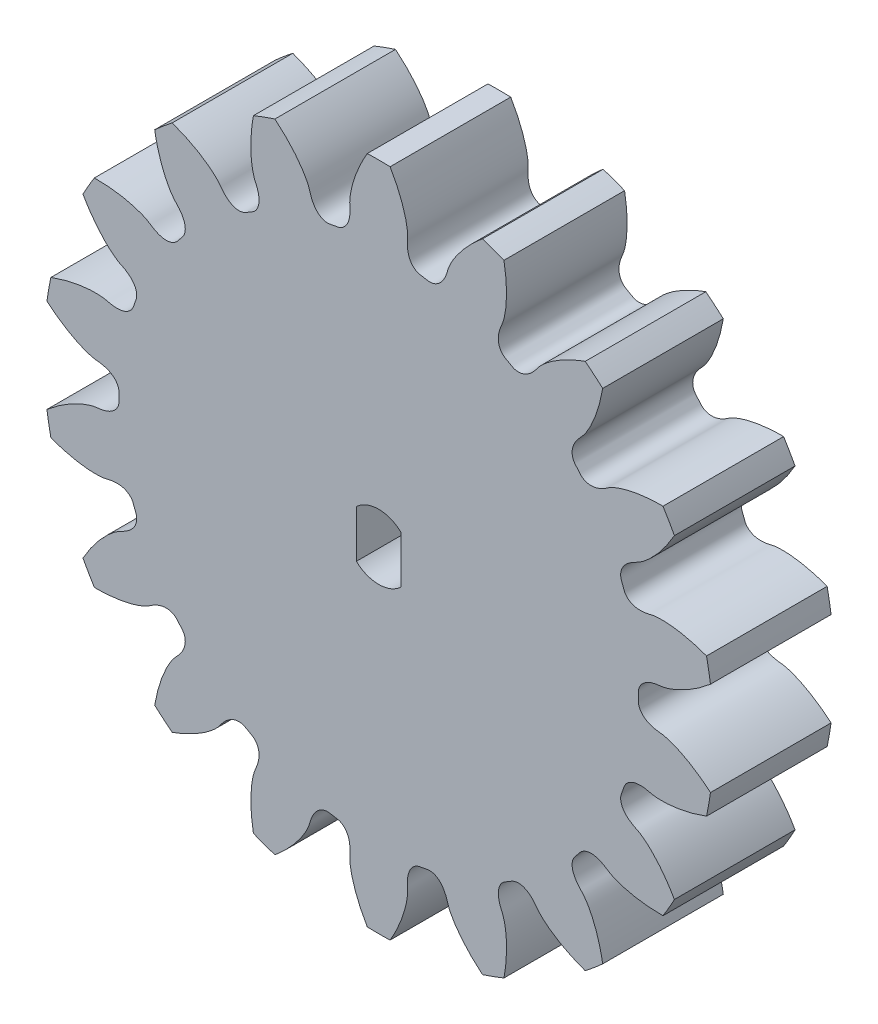
SolidWorks part; units mm, degrees
ref_plane "Front Plane" through (0, 0, 0) normal (0, 0, 1) x (1, 0, 0)
ref_plane "Top Plane" through (0, 0, 0) normal (0, 1, 0) x (1, 0, 0)
ref_plane "Right Plane" through (0, 0, 0) normal (1, 0, 0) x (0, 0, -1)
ref_axis "Axis1" through (0, 0, 55) along (0, 0, -1)
sketch "旋转草图小直齿轮" plane through (0, 0, 0) normal (1, 0, 0) x (0, 0, -1)
  line L0 (0, 0) -> (1, 0) construction
  line L1 (-5, 0) -> (-5, 27.7778)
  line L2 (-5, 27.7778) -> (5, 27.7778)
  line L3 (5, 27.7778) -> (5, 0)
  line L4 (5, 0) -> (-5, 0)
  dimension "Side1" = 5
  dimension "OutsideRadius" = 27.7778
  dimension "Side2" = 5
revolve "小直齿轮" add sketch "旋转草图小直齿轮" angle 360 about L0
sketch "齿草图小直齿轮" plane through (0, 0, 0) normal (0, 0, 1) x (1, 0, 0)
  arc A0 (27.6292, 3.9957) -> (27.6292, -3.9957) centre (0, 0) cw
  spline S0 degree 3 poles (27.6292, -3.9957) (27.2908, -3.7024) (26.835, -3.3411) (26.2533, -2.941) (25.9375, -2.7384) (25.6361, -2.5584) (25.3503, -2.4) (25.0811, -2.2618) (24.8295, -2.1426) (24.5964, -2.0413) (24.3827, -1.9564) (24.1891, -1.8866) (24.0164, -1.8305) (23.8653, -1.7866) (23.7363, -1.7537) (23.63, -1.73) (23.5467, -1.7143) (23.4869, -1.7049) (23.4509, -1.7003) (23.38, -1.6938) (23.295, -1.6872) (23.1887, -1.6741) (23.1121, -1.6633) (23.037, -1.6511) (22.9632, -1.6375) (22.8908, -1.6224) (22.8198, -1.606) (22.75, -1.5881) (22.6816, -1.5687) (22.6144, -1.5478) (22.5484, -1.5253) (22.4835, -1.501) (22.4198, -1.4751) (22.3571, -1.4472) (22.2955, -1.4174) (22.2348, -1.3853) (22.1752, -1.3509) (22.1164, -1.3139) (22.0587, -1.2741) (22.0019, -1.2311) (21.9462, -1.1846) (21.8918, -1.1343) (21.8389, -1.0798) (21.7878, -1.0207) (21.739, -0.9566) (21.693, -0.8872) (21.6507, -0.8122) (21.6129, -0.7318) (21.5807, -0.646) (21.5549, -0.5554) (21.5367, -0.4609) (21.5277, -0.3711) (21.5238, -0.2172) (21.531, 0) (21.5238, 0.2172) (21.5277, 0.3711) (21.5367, 0.4609) (21.5549, 0.5554) (21.5807, 0.646) (21.6129, 0.7318) (21.6507, 0.8122) (21.693, 0.8872) (21.739, 0.9566) (21.7878, 1.0207) (21.8389, 1.0798) (21.8918, 1.1343) (21.9462, 1.1846) (22.0019, 1.2311) (22.0587, 1.2741) (22.1164, 1.3139) (22.1752, 1.3509) (22.2348, 1.3853) (22.2955, 1.4174) (22.3571, 1.4472) (22.4198, 1.4751) (22.4835, 1.501) (22.5484, 1.5253) (22.6144, 1.5478) (22.6816, 1.5687) (22.75, 1.5881) (22.8198, 1.606) (22.8908, 1.6224) (22.9632, 1.6375) (23.037, 1.6511) (23.1121, 1.6633) (23.1887, 1.6741) (23.295, 1.6872) (23.38, 1.6938) (23.4509, 1.7003) (23.4869, 1.7049) (23.5467, 1.7143) (23.63, 1.73) (23.7363, 1.7537) (23.8653, 1.7866) (24.0164, 1.8305) (24.1891, 1.8866) (24.3827, 1.9564) (24.5964, 2.0413) (24.8295, 2.1426) (25.0811, 2.2618) (25.3503, 2.4) (25.6361, 2.5584) (25.9375, 2.7384) (26.2533, 2.941) (26.835, 3.3411) (27.2908, 3.7024) (27.6292, 3.9957) knots 0 0 0 0 0.086682 0.112454 0.136665 0.159314 0.1804 0.199925 0.217888 0.234288 0.249127 0.262404 0.274119 0.284272 0.292862 0.299891 0.305358 0.309263 0.311606 0.312387 0.323046 0.328118 0.333109 0.338022 0.342862 0.347631 0.352335 0.356978 0.361567 0.366106 0.370604 0.375067 0.379505 0.383926 0.388341 0.392762 0.397202 0.401675 0.406197 0.410784 0.415455 0.420228 0.425122 0.430157 0.43535 0.440715 0.446262 0.451994 0.457907 0.463985 0.470202 0.476522 0.481419 0.5 0.518581 0.523478 0.529798 0.536015 0.542093 0.548006 0.553738 0.559285 0.56465 0.569843 0.574878 0.579772 0.584545 0.589216 0.593803 0.598325 0.602798 0.607238 0.611659 0.616074 0.620495 0.624933 0.629396 0.633894 0.638433 0.643022 0.647665 0.652369 0.657138 0.661978 0.666891 0.671882 0.676954 0.687613 0.688394 0.690737 0.694642 0.700109 0.707138 0.715728 0.725881 0.737596 0.750873 0.765712 0.782112 0.800075 0.8196 0.840686 0.863335 0.887546 0.913318 1 1 1 1
extrude "齿拉伸切除小直齿轮" cut sketch "齿草图小直齿轮" against normal blind 9.525 and the other way blind 9.525
pattern_circular "齿形小直齿轮" count 18 every 20 about axis through (0, 0, 55) along (0, 0, -1) of "齿拉伸切除小直齿轮"
sketch "辅助草图小直齿轮" plane through (0, 0, 0) normal (0, 0, 1) x (1, 0, 0)
  circle A0 centre (0, 0) radius 25 construction
  circle A1 centre (0, 0) radius 23.4923 construction
  circle A2 centre (0, 0) radius 23.4923 construction
  circle A3 centre (0, 0) radius 27.7778 construction
  circle A4 centre (0, 0) radius 21.5278 construction
  dimension "PitchDiameter" = 50
  dimension "BaseDiameter" = 46.9846
  dimension "FormDiameter" = 46.9846
  dimension "MajorDiameter" = 55.5556
  dimension "MinorDiameter" = 43.0556
sketch "Sketch5" plane through (0, 0, 5) normal (0, 0, 1) x (1, 0, 0)
  line L2 (-1.85, 1.9666) -> (-1.85, -1.9666)
  line L4 (1.85, 1.9666) -> (1.85, -1.9666)
  arc A1 (-1.85, 1.9666) -> (1.85, 1.9666) centre (0, 0) cw
  arc A2 (-1.85, -1.9666) -> (1.85, -1.9666) centre (0, 0) ccw
  dimension "D1" = 2.7
  dimension "D2" = 3.7
extrude "Cut-Extrude2" cut sketch "Sketch5" against normal blind 7.5
